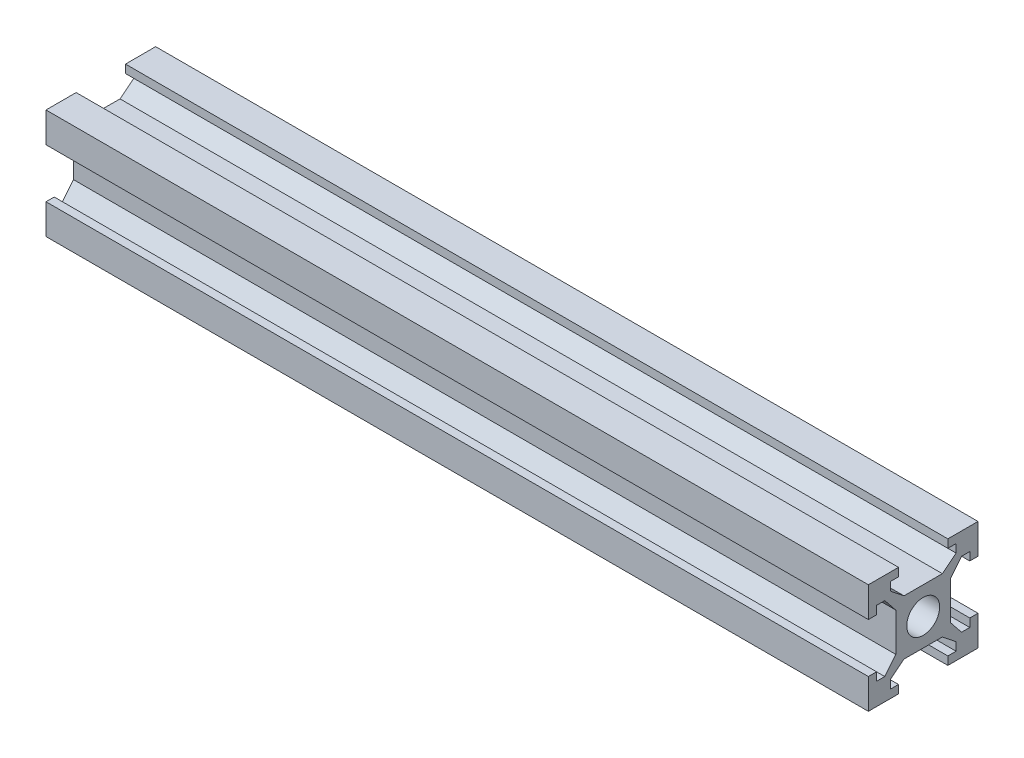
SolidWorks part; units mm, degrees
ref_plane "Front Plane" through (0, 0, 0) normal (0, 0, 1) x (1, 0, 0)
ref_plane "Top Plane" through (0, 0, 0) normal (0, 1, 0) x (1, 0, 0)
ref_plane "Right Plane" through (0, 0, 0) normal (1, 0, 0) x (0, 0, -1)
sketch "Sketch1" plane through (0, 0, 0) normal (1, 0, 0) x (0, 0, -1)
  line L1 (-10, 10) -> (10, 10)
  line L2 (-10, 10) -> (-10, -10)
  line L3 (-10, -10) -> (10, -10)
  line L4 (10, 10) -> (10, -10)
  line L5 (-10, 10) -> (10, -10) construction
  line L6 (-10, -10) -> (10, 10) construction
  point P0 (0, 0)
  dimension "D1" = 20
  dimension "D2" = 20
extrude "Boss-Extrude1" add sketch "Sketch1" along normal blind 150
sketch "Sketch2" plane through (150, 0, 0) normal (1, 0, 0) x (0, 0, -1)
  line L0 (0, 0) -> (0, 10) construction
  line L1 (10, 10) -> (-10, 10) construction
  line L2 (-4.5, 10) -> (-4.5, 8.5)
  line L3 (-4.5, 8.5) -> (-6, 8.5)
  line L4 (-6, 8.5) -> (-6, 7)
  line L5 (-6, 7) -> (-3.5, 5)
  line L6 (-3.5, 5) -> (3.5, 5)
  line L7 (-4.5, 10) -> (4.5, 10)
  line L8 (6, 7) -> (3.5, 5)
  line L9 (6, 8.5) -> (6, 7)
  line L10 (4.5, 8.5) -> (6, 8.5)
  line L11 (4.5, 10) -> (4.5, 8.5)
  circle A0 centre (0, 0) radius 3
  point P14 (0, 5)
  line M2 (10, 10) -> (-10, 10)
  dimension "D1" = 6
  dimension "D2" = 4.5
  dimension "D3" = 3.5
  dimension "D4" = 1.5
  dimension "D5" = 1.5
  dimension "D6" = 2
extrude "Cut-Extrude1" cut sketch "Sketch2" against normal through all contours A0 region at (150, 0, 0)
extrude "Cut-Extrude2" cut sketch "Sketch2<3>" against normal through all contours L0 L6 L8 L9 L10 L11 M2 | L6 L0 L7 L2 L3 L4 L5 region at (150, 7.5256, 2.585) region at (150, 7.5256, -2.585)
sketch "Sketch2<3>" plane through (150, 0, 0) normal (1, 0, 0) x (0, 0, -1) same geometry as "Sketch2"
pattern_circular "CirPattern1" count 4 every 90 about axis through (0, 0, 0) along (1, 0, 0) of "Cut-Extrude2"
